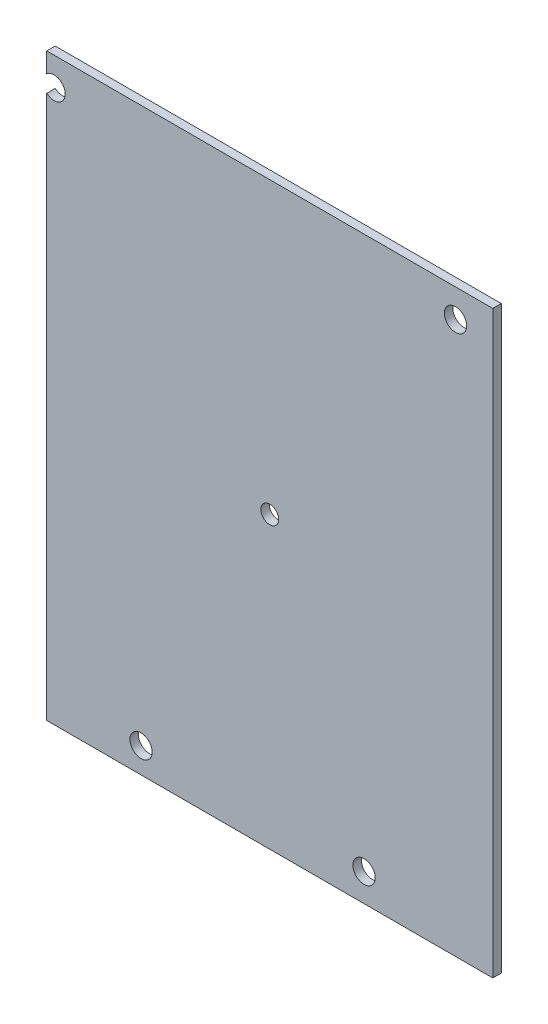
SolidWorks part; units mm, degrees
ref_plane "Front Plane" through (0, 0, 0) normal (0, 0, 1) x (1, 0, 0)
ref_plane "Top Plane" through (0, 0, 0) normal (0, 1, 0) x (1, 0, 0)
ref_plane "Right Plane" through (0, 0, 0) normal (1, 0, 0) x (0, 0, -1)
sketch "Sketch1" plane through (0, 0, 0) normal (0, 0, 1) x (1, 0, 0)
  line L1 (-35.7776, 74.5094) -> (64.2224, 74.5094)
  line L2 (-35.7776, 74.5094) -> (-35.7776, -55.4906)
  line L3 (-35.7776, -55.4906) -> (64.2224, -55.4906)
  line L4 (64.2224, 74.5094) -> (64.2224, -55.4906)
  dimension "D1" = 100
  dimension "D2" = 130
base flange "Base-Flange1" sketch "Sketch1" thickness 1.8974 reverse thickness direction no parameters "D1"=2.54
sketch "Sketch6" plane through (0, 0, 0) normal (0, 0, 1) x (1, 0, 0)
  line L0 (64.2224, 74.5094) -> (-35.7776, 74.5094) construction
  line L1 (-35.7776, 74.5094) -> (-35.7776, -55.4906) construction
  circle A0 centre (-34.1334, 68.1735) radius 2.5
  circle A1 centre (55.8666, 68.1735) radius 2.5
  circle A2 centre (35.3632, -49.2465) radius 2.5
  circle A3 centre (-14.6334, -49.8265) radius 2.5
  circle A4 centre (14.2224, 9.5094) radius 2
  point P12 (14.2224, 74.5094)
  point P13 (-35.7776, 9.5094)
  dimension "D1" = 5
extrude "Cut-Extrude1" cut sketch "Sketch6" against normal blind 2 normal cut yes
sketch "Bend-Lines1" plane through (0, 0, 0) normal (0, 1, 0) x (1, 0, 0)
sketch "Bounding-Box1" plane through (0, 0, 0) normal (0, 1, 0) x (1, 0, 0)
sheet metal parameters "Sheet-Metal1" thickness 1.8974 parameters "D1"=2.54
flat pattern "Flat-Pattern1" [suppressed]
sketch "Bend-Lines2" plane through (0, 0, 0) normal (0, 1, 0) x (1, 0, 0)
sketch "Bounding-Box2" [suppressed] plane through (0, 0, 0) normal (0, 1, 0) x (1, 0, 0)
sheet metal parameters "Sheet-Metal2" thickness 1.8974 parameters "D1"=2.54
flat pattern "Flat-Pattern1"
sketch "Bend-Lines2" plane through (0, 0, 0) normal (0, 1, 0) x (1, 0, 0)
sketch "Bounding-Box2" [suppressed] plane through (0, 0, 0) normal (0, 1, 0) x (1, 0, 0)
